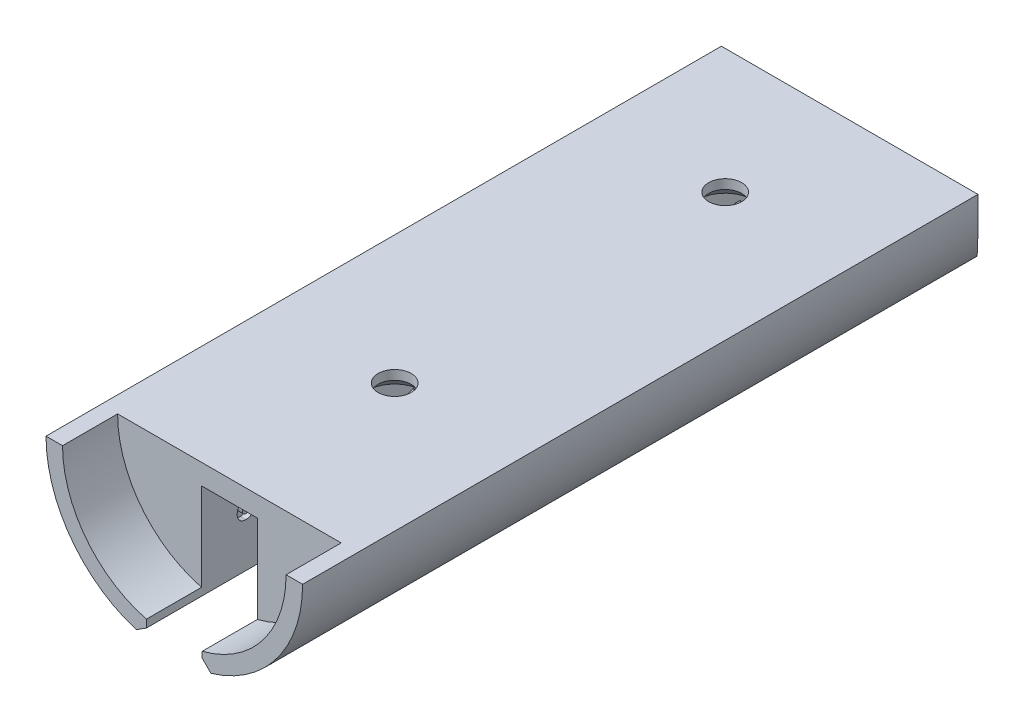
SolidWorks part; units mm, degrees
ref_plane "Front Plane" through (0, 0, 0) normal (0, 0, 1) x (1, 0, 0)
ref_plane "Top Plane" through (0, 0, 0) normal (0, 1, 0) x (1, 0, 0)
ref_plane "Right Plane" through (0, 0, 0) normal (1, 0, 0) x (0, 0, -1)
sketch "Sketch1" plane through (0, 0, 0) normal (0, 0, 1) x (1, 0, 0)
  line L1 (-14.7902, 8.509) -> (14.7902, 8.509)
  line L2 (3.0226, 5.969) -> (-3.0226, 5.969) construction
  line L11 (3.2131, -6.1595) -> (3.2131, 6.1595)
  line L12 (3.2131, 6.1595) -> (-3.2131, 6.1595)
  line L13 (-3.2131, 6.1595) -> (-3.2131, -6.1595)
  line L14 (-3.2131, -6.1595) -> (3.2131, -6.1595)
  line L15 (3.2131, -6.1595) -> (3.2131, 6.1595)
  line L16 (3.2131, 6.1595) -> (-3.2131, 6.1595)
  line L17 (-3.2131, 6.1595) -> (-3.2131, -6.1595)
  line L18 (-3.2131, -6.1595) -> (3.2131, -6.1595)
  arc A0 (-14.7902, 8.509) -> (14.7902, 8.509) centre (0, 8.509) ccw
  dimension "D1" = 2.54
  dimension "D2" = 0.1905
extrude "Boss-Extrude1" add sketch "Sketch1" along normal mid plane 190.5 contours L1 A0 L17 L16 L15 region at (0, 8.1798, 0)
sketch "Sketch2" plane through (0, 0, 95.25) normal (0, 0, 1) x (1, 0, 0)
  line L0 (-14.7902, 8.509) -> (14.7902, 8.509) construction
  line L1 (-12.8852, 8.509) -> (12.8852, 8.509)
  circle A0 centre (0, 8.509) radius 12.8852
  arc A2 (-14.7902, 8.509) -> (-3.2131, -5.9279) centre (0, 8.509) ccw construction
  line M2 (14.7902, 8.509) -> (-14.7902, 8.509)
  line M4 (-3.2131, -5.9279) -> (-3.2131, 6.1595)
  line M5 (-3.2131, 6.1595) -> (3.2131, 6.1595)
  line M6 (3.2131, 6.1595) -> (3.2131, -5.9279)
  dimension "D1" = 1.905
extrude "Cut-Extrude1" cut sketch "Sketch2" against normal blind 6.35 contours A0 M2 M4 M5 M6 region at (0, 8.2227, 95.25)
sketch "Sketch3" plane through (0, 0, -95.25) normal (0, 0, -1) x (-1, 0, 0)
  line L8 (12.8852, 8.509) -> (-12.8852, 8.509)
  line L9 (3.2131, 6.1595) -> (3.2131, -3.9691)
  line L10 (-3.2131, 6.1595) -> (3.2131, 6.1595)
  line L11 (-3.2131, -3.9691) -> (-3.2131, 6.1595)
  line L12 (12.8852, 8.509) -> (-12.8852, 8.509)
  line L13 (3.2131, 6.1595) -> (3.2131, -3.9691)
  line L14 (-3.2131, 6.1595) -> (3.2131, 6.1595)
  line L15 (-3.2131, -3.9691) -> (-3.2131, 6.1595)
  line L16 (14.7902, 8.509) -> (-14.7902, 8.509)
  line L17 (-3.2131, -5.9279) -> (-3.2131, 6.1595)
  line L18 (-3.2131, 6.1595) -> (3.2131, 6.1595)
  line L19 (3.2131, 6.1595) -> (3.2131, -5.9279)
  line L20 (14.7902, 8.509) -> (-14.7902, 8.509)
  line L21 (-3.2131, -5.9279) -> (-3.2131, 6.1595)
  line L22 (-3.2131, 6.1595) -> (3.2131, 6.1595)
  line L23 (3.2131, 6.1595) -> (3.2131, -5.9279)
  circle A2 centre (0, 8.509) radius 12.5042
  arc A4 (3.2131, -3.9691) -> (12.8852, 8.509) centre (0, 8.509) ccw
  arc A5 (-12.8852, 8.509) -> (-3.2131, -3.9691) centre (0, 8.509) ccw
  arc A6 (3.2131, -3.9691) -> (12.8852, 8.509) centre (0, 8.509) ccw
  arc A7 (-12.8852, 8.509) -> (-3.2131, -3.9691) centre (0, 8.509) ccw
  arc A9 (-14.7902, 8.509) -> (-3.2131, -5.9279) centre (0, 8.509) ccw
  arc A10 (3.2131, -5.9279) -> (14.7902, 8.509) centre (0, 8.509) ccw
  arc A11 (-14.7902, 8.509) -> (-3.2131, -5.9279) centre (0, 8.509) ccw
  arc A12 (3.2131, -5.9279) -> (14.7902, 8.509) centre (0, 8.509) ccw
  line M14 (14.7902, 8.509) -> (-14.7902, 8.509)
  arc M15 (-14.7902, 8.509) -> (-3.2131, -5.9279) centre (0, 8.509) ccw
  line M16 (-3.2131, -5.9279) -> (-3.2131, 6.1595)
  line M18 (3.2131, 6.1595) -> (3.2131, -5.9279)
  arc M19 (3.2131, -5.9279) -> (14.7902, 8.509) centre (0, 8.509) ccw
  dimension "D2" = 0.381
  dimension "D1" = 0
  dimension "D3" = 0
extrude "Cut-Extrude2" cut sketch "Sketch3" against normal blind 5.969 contours A6 M18 M19 M14 | A7 M14 M15 M16 | A7 A2 M14 M16 | L23 A6 A2 M14 region at (-10.0592, 0.7119, -95.25) region at (-13.8377, 8.3239, -95.25) region at (10.0381, 0.7912, -95.25) region at (10.3303, 0.5018, -95.25)
sketch "Sketch4" plane through (0, 6.1595, 0) normal (0, -1, 0) x (1, 0, 0)
  line L1 (0, -95.25) -> (0, 88.9) construction
  line L2 (3.2131, -95.25) -> (-3.2131, -95.25) construction
  line L3 (-3.2131, 88.9) -> (3.2131, 88.9) construction
  circle A0 centre (0, -44.45) radius 1.905
  circle A1 centre (0, 69.85) radius 1.905
  circle A2 centre (0, 31.75) radius 1.905
  dimension "D1" = 3.81
  dimension "D2" = 76.2
  dimension "D3" = 38.1
  dimension "D4" = 19.05
extrude "Cut-Extrude3" cut sketch "Sketch4" against normal through all
chamfer "Chamfer1" distance 1.27 angle 45 2 edges at (3.2131, -5.9279, 2.9845) (-3.2131, -5.9279, 2.9845) first distance on face at (3.2131, -1.8282, -0.0952) first distance on face at (-10.27, 0.2734, 2.9845)
chamfer "Chamfer2" distance 1.27 angle 45 3 edges at (0, 6.1595, 71.755) (0, 6.1595, -46.355) (0, 6.1595, 29.845)
sketch "Sketch5" plane through (-3.2131, 0, 0) normal (1, 0, 0) x (0, 0, -1)
  line L0 (-3.7765, 3.6195) -> (-88.9, 3.6195) construction
  line L1 (-88.9, 6.1595) -> (95.25, 6.1595) construction
  line L2 (-88.9, -3.9691) -> (-88.9, 6.1595) construction
  text T0 "<b>Ceiling LED Mount Tee End V2   </b>" font "Century Gothic" height 3.302
  point P2 (0, 3.6195)
  dimension "D1" = 2.54
extrude "Cut-Extrude4" cut sketch "Sketch5" against normal blind 0.635
sketch "Sketch9" plane through (0, 0, -89.281) normal (0, 0, -1) x (-1, 0, 0)
  line L3 (3.2131, -3.5753) -> (3.2131, -4.8637)
  line L4 (3.2131, -4.8637) -> (4.3927, -5.6138)
  line L5 (14.7902, 8.509) -> (12.5042, 8.509)
  line L6 (3.2131, -3.5753) -> (3.2131, -4.8637)
  line L7 (3.2131, -4.8637) -> (4.3927, -5.6138)
  line L8 (14.7902, 8.509) -> (12.5042, 8.509)
  line L9 (-4.2212, -5.666) -> (-3.2131, -4.6579)
  line L10 (-3.2131, -4.6579) -> (-3.2131, -3.5753)
  line L11 (-12.5042, 8.509) -> (-14.7902, 8.509)
  line L12 (-4.2212, -5.666) -> (-3.2131, -4.6579)
  line L13 (-3.2131, -4.6579) -> (-3.2131, -3.5753)
  line L14 (-12.5042, 8.509) -> (-14.7902, 8.509)
  arc A2 (4.3927, -5.6138) -> (14.7902, 8.509) centre (0, 8.509) ccw
  arc A3 (3.2131, -3.5753) -> (12.5042, 8.509) centre (0, 8.509) ccw
  arc A4 (-4.2212, -5.666) -> (4.3927, -5.6138) centre (0, 8.509) ccw
  arc A5 (-3.2131, -3.5753) -> (3.2131, -3.5753) centre (0, 8.509) ccw
  arc A6 (-14.7902, 8.509) -> (-4.2212, -5.666) centre (0, 8.509) ccw
  arc A7 (-12.5042, 8.509) -> (-3.2131, -3.5753) centre (0, 8.509) ccw
  line M11 (3.2131, -3.5753) -> (3.2131, -4.8637)
  line M12 (3.2131, -4.8637) -> (4.3927, -5.6138)
  dimension "D1" = 0
  dimension "D2" = 0
extrude "Boss-Extrude2" add sketch "Sketch9" against normal blind 109.22 contours A5 L13 L12 A4 M12 M11 region at (-0.0004, -5.044, -89.281)
sketch "Sketch8" plane through (0, 0, 0) normal (1, 0, 0) x (0, 0, -1)
  line L0 (-95.25, 8.509) -> (89.281, 8.509) construction
  line L1 (89.281, 8.509) -> (95.25, 8.509) construction
  line L4 (89.281, -6.2812) -> (89.281, 8.509) construction
  line L6 (89.281, 8.509) -> (95.25, 8.509)
  line L9 (89.281, -6.2812) -> (89.281, -3.5753)
  line L11 (-16.4084, 8.509) -> (89.281, 8.509)
  line L12 (-88.9, -3.9691) -> (-88.9, 6.1595) construction
  line L13 (-19.939, -6.2812) -> (89.281, -6.2812) construction
  line L14 (-19.939, -6.2812) -> (89.281, -6.2812)
  line L17 (95.25, -3.9952) -> (95.25, 8.509)
  line L18 (89.281, -3.9952) -> (95.25, -3.9952)
  arc A0 (-16.4084, 8.509) -> (-2.2334, -5.666) centre (-2.2334, 8.509) ccw
  circle A1 centre (-2.2334, 8.509) radius 15.1638
  point P13 (-2.2334, 8.509)
  point P16 (0, 0)
  point P17 (0, 0)
  dimension "D2" = 30.3276
  dimension "D1" = 72.4916
extrude "Cut-Extrude7" cut sketch "Sketch8" against normal through all both and the other way through all contours A1 L9 L6 L11 | A1 L11 A0 | L11 A1 A0 region at (0, 1.0384, -52.0965) region at (0, 8.5436, 2.2334)
